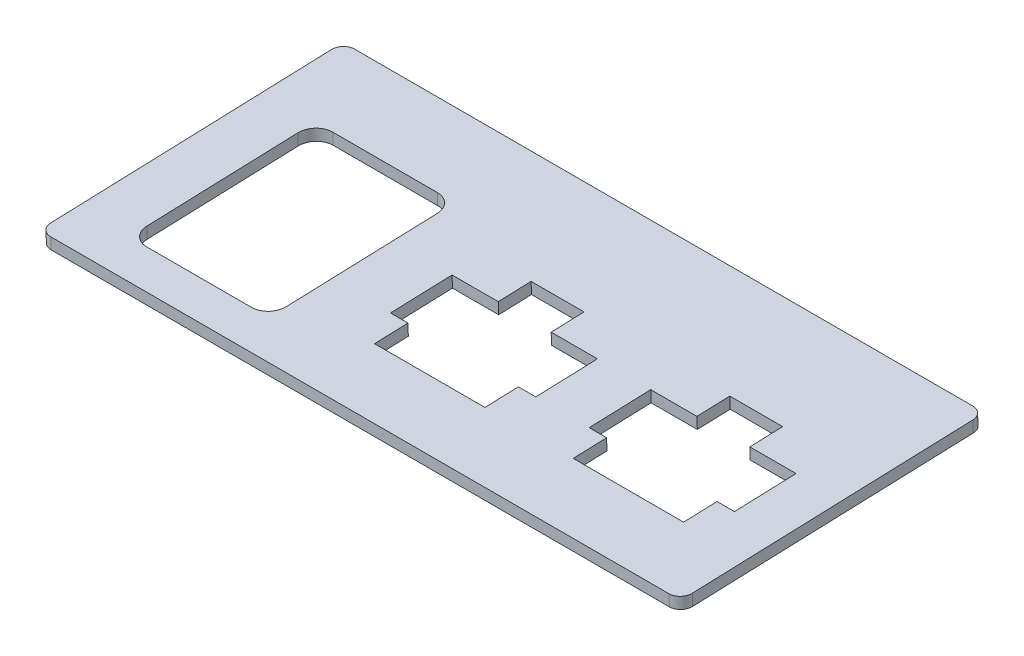
SolidWorks part; units mm, degrees
ref_plane "Front Plane" through (0, 0, 0) normal (0, 0, 1) x (1, 0, 0)
ref_plane "Top Plane" through (0, 0, 0) normal (0, 1, 0) x (1, 0, 0)
ref_plane "Right Plane" through (0, 0, 0) normal (1, 0, 0) x (0, 0, -1)
sketch "Sketch1" plane through (0, -71.9872, -2.5138) normal (0, 0.9994, 0.0349) x (1, 0, 0)
  line L0 (-56.175, 48.6398) -> (56.175, 48.6398) construction
  line L1 (-53.6759, -2.9116) -> (-56.175, -2.9116) construction
  line L8 (-55.175, -4.4116) -> (55.175, -4.4116)
  line L9 (55.175, -4.4116) -> (55.175, 47.8898)
  line L10 (55.175, 47.8898) -> (-55.175, 47.8898)
  line L11 (-55.175, 47.8898) -> (-55.175, -4.4116)
  dimension "D4" = 0.75
  dimension "D1" = 1.5
  dimension "D2" = 3.0034
  dimension "D3" = 3.0034
extrude "Boss-Extrude1" add sketch "Sketch1" along normal blind 2
sketch "Sketch2" plane through (0, -71.9872, -2.5138) normal (0, -0.9994, -0.0349) x (1, 0, 0)
  line L0 (-4.05, -23.4641) -> (-4.05, -29.1141)
  line L1 (-43.175, -2.1141) -> (-25.175, -2.1141)
  line L2 (-46.175, -5.1141) -> (-46.175, -31.1141)
  line L3 (-43.175, -34.1141) -> (-25.175, -34.1141)
  line L4 (-22.175, -5.1141) -> (-22.175, -31.1141)
  line L5 (-12, -12.8641) -> (-9, -12.8641)
  line L6 (-12, -12.8641) -> (-12, -23.4641)
  line L7 (-12, -23.4641) -> (-4.05, -23.4641)
  line L8 (13, -12.8641) -> (13, -23.4641)
  line L9 (-9, -7.1141) -> (10, -7.1141)
  line L10 (-9, -7.1141) -> (-9, -12.8641)
  line L11 (-4.05, -29.1141) -> (5.05, -29.1141)
  line L12 (10, -7.1141) -> (10, -12.8641)
  line L13 (10, -12.8641) -> (13, -12.8641)
  line L14 (5.05, -23.4641) -> (5.05, -29.1141)
  line L15 (5.05, -23.4641) -> (13, -23.4641)
  line L16 (-13, -4.6141) -> (14, -31.6141) construction
  line L17 (-13, -4.6141) -> (14, -4.6141) construction
  line L18 (-13, -4.6141) -> (-13, -31.6141) construction
  line L19 (-13, -31.6141) -> (14, -31.6141) construction
  line L20 (14, -4.6141) -> (14, -31.6141) construction
  line L21 (17.5875, 3.7502) -> (17.5875, -36.664) construction
  line L22 (47.175, -18.1641) -> (22.175, -18.1641) construction
  line L23 (34.675, -7.1141) -> (34.675, -29.1141) construction
  line L24 (21.175, -4.6141) -> (21.175, -31.6141) construction
  line L25 (48.175, -31.6141) -> (21.175, -31.6141) construction
  line L26 (48.175, -4.6141) -> (48.175, -31.6141) construction
  line L27 (48.175, -4.6141) -> (21.175, -4.6141) construction
  line L28 (-48.175, -18.1141) -> (-46.175, -18.1141) construction
  line L29 (-48.175, -0.1141) -> (-20.175, -0.1141) construction
  line L30 (-48.175, -0.1141) -> (-48.175, -36.1141) construction
  line L31 (-48.175, -36.1141) -> (-20.175, -36.1141) construction
  line L32 (-20.175, -0.1141) -> (-20.175, -36.1141) construction
  line L33 (-34.175, -2.1141) -> (-34.175, -0.1141) construction
  line L34 (0.5, -7.1141) -> (0.5, -29.1141) construction
  line L35 (-12, -18.1641) -> (13, -18.1641) construction
  line L36 (48.175, -4.6141) -> (21.175, -31.6141) construction
  line L37 (30.125, -23.4641) -> (22.175, -23.4641)
  line L38 (30.125, -23.4641) -> (30.125, -29.1141)
  line L39 (25.175, -12.8641) -> (22.175, -12.8641)
  line L40 (25.175, -7.1141) -> (25.175, -12.8641)
  line L41 (39.225, -29.1141) -> (30.125, -29.1141)
  line L42 (44.175, -7.1141) -> (44.175, -12.8641)
  line L43 (44.175, -7.1141) -> (25.175, -7.1141)
  line L44 (22.175, -12.8641) -> (22.175, -23.4641)
  line L45 (47.175, -23.4641) -> (39.225, -23.4641)
  line L46 (47.175, -12.8641) -> (47.175, -23.4641)
  line L47 (47.175, -12.8641) -> (44.175, -12.8641)
  line L48 (39.225, -23.4641) -> (39.225, -29.1141)
  line L49 (21.175, -18.1141) -> (14, -18.1141) construction
  line L50 (-55.175, 4.4116) -> (55.175, 4.4116) construction
  line L51 (48.175, -18.1141) -> (52.175, -18.1141) construction
  line L52 (55.175, 4.4116) -> (55.175, -47.8898) construction
  line L53 (-46.7914, -40.6398) -> (46.7914, -40.6398) construction
  line L54 (-13, -18.1141) -> (-20.175, -18.1141) construction
  line L55 (-34.175, -0.1141) -> (-34.175, 4.4116) construction
  line L56 (-34.175, -36.1141) -> (-34.175, -40.6398) construction
  line L57 (-55.175, -47.8898) -> (-55.175, 4.4116) construction
  line L58 (-48.175, -18.1141) -> (-52.175, -18.1141) construction
  arc A0 (-46.175, -31.1141) -> (-43.175, -34.1141) centre (-43.175, -31.1141) ccw
  arc A1 (-25.175, -34.1141) -> (-22.175, -31.1141) centre (-25.175, -31.1141) ccw
  arc A2 (-25.175, -2.1141) -> (-22.175, -5.1141) centre (-25.175, -5.1141) cw
  arc A3 (-43.175, -2.1141) -> (-46.175, -5.1141) centre (-43.175, -5.1141) ccw
  point P28 (0.5, -18.1141)
  point P63 (34.675, -18.1141)
  dimension "D1" = 3
  dimension "D2" = 32
  dimension "D3" = 24
  dimension "D4" = 28
  dimension "D5" = 36
  dimension "D6" = 25
  dimension "D7" = 22
  dimension "D8" = 10.6
  dimension "D9" = 19
  dimension "D10" = 9.1
  dimension "D11" = 5.75
  dimension "D12" = 27
  dimension "D13" = 27
  dimension "D14" = 4
  dimension "D15" = 3
  dimension "D16" = 3
extrude "Cut-Extrude1" cut sketch "Sketch2" against normal up to next
fillet "Fillet1" radius 2 4 edges at (-55.175, -71.1418, 1.93) (55.175, -71.1418, 1.93) (55.175, -69.3165, -50.3395) (-55.175, -69.3165, -50.3395)
